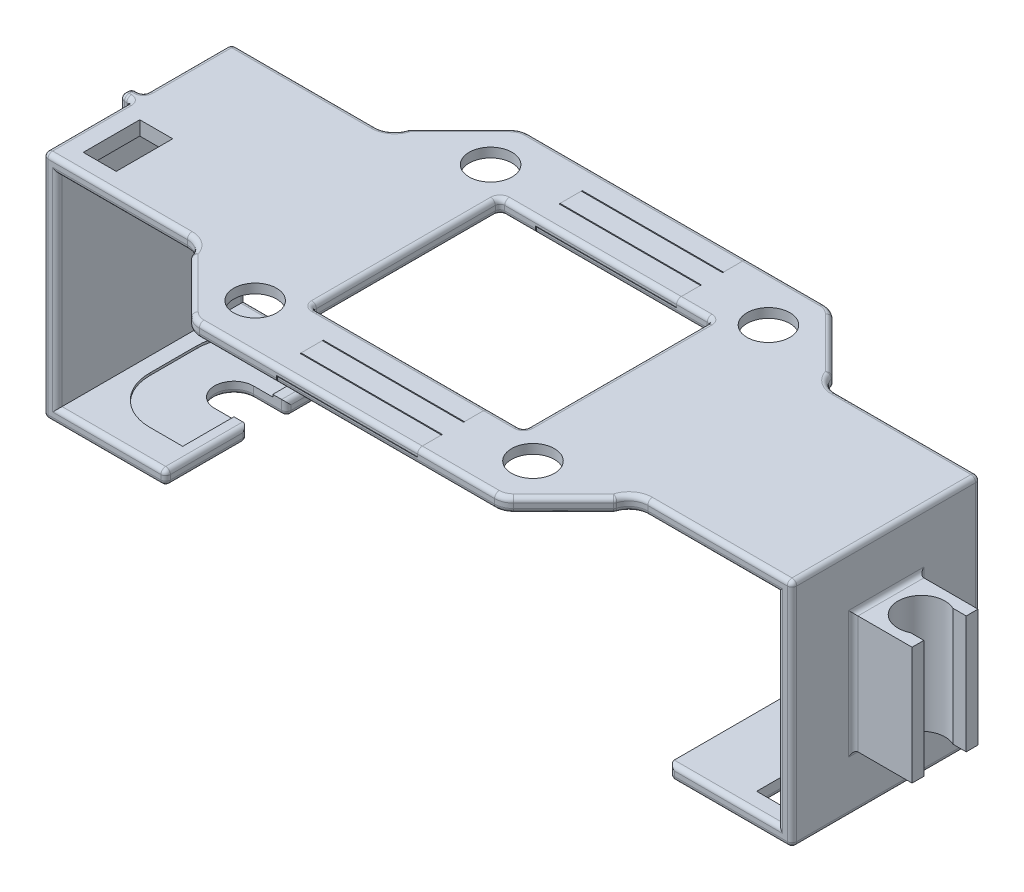
SolidWorks part; units mm, degrees
ref_plane "Front" through (0, 0, 0) normal (0, 0, 1) x (1, 0, 0)
ref_plane "Top" through (0, 0, 0) normal (0, 1, 0) x (1, 0, 0)
ref_plane "Right" through (0, 0, 0) normal (1, 0, 0) x (0, 0, -1)
sketch "Sketch2" plane through (0, 0, 0) normal (0, 1, 0) x (1, 0, 0)
  line L0 (45, -20) -> (52.5, -20)
  line L1 (-52.5, 20) -> (-45, 20)
  line L2 (-52.5, 20) -> (-52.5, -20) construction
  line L3 (-52.5, -20) -> (-45, -20)
  line L4 (52.5, 20) -> (52.5, -20) construction
  line L5 (-52.5, 20) -> (52.5, -20) construction
  line L6 (-52.5, -20) -> (52.5, 20) construction
  line L7 (-52.5, 20) -> (-76.5, 20)
  line L8 (-76.5, 20) -> (-76.5, -20) construction
  line L9 (-76.5, -20) -> (-52.5, -20)
  line L10 (52.5, -20) -> (76.5, -20)
  line L11 (76.5, -20) -> (76.5, 20) construction
  line L12 (76.5, 20) -> (52.5, 20)
  line L13 (-76.5, -20) -> (-79.5, -20)
  line L14 (-79.5, -20) -> (-79.5, 20)
  line L15 (-79.5, 20) -> (-76.5, 20)
  line L16 (76.5, -20) -> (79.5, -20)
  line L17 (79.5, -20) -> (79.5, 20)
  line L18 (79.5, 20) -> (76.5, 20)
  line L19 (-45, 20) -> (-45, 35)
  line L20 (-45, 35) -> (45, 35)
  line L21 (45, 35) -> (45, 20)
  line L22 (45, -20) -> (45, -35)
  line L23 (45, -35) -> (-45, -35)
  line L24 (-45, -35) -> (-45, -20)
  line L25 (45, 20) -> (52.5, 20)
  line L26 (0, -35) -> (0, 35) construction
  dimension "D1" = 40
  dimension "D2" = 105
  dimension "D3" = 24
  dimension "D4" = 3
  dimension "D5" = 15
  dimension "D6" = 90
extrude "Boss-Extrude1" add sketch "Sketch2" along normal blind 3
sketch "Sketch4" plane through (0, 0, -20) normal (0, 0, -1) x (-1, 0, 0)
  line L0 (79.5, 0) -> (79.5, -46)
  line L1 (79.5, -46) -> (53.5, -46)
  line L2 (53.5, -46) -> (53.5, -43)
  line L3 (53.5, -43) -> (76.5, -43)
  line L4 (76.5, -43) -> (76.5, 0)
  line L5 (45, 0) -> (79.5, 0) construction
  line L6 (76.5, 0) -> (79.5, 0)
  line L7 (52.5, 0) -> (76.5, 0) construction
  dimension "D1" = 43
  dimension "D2" = 23
extrude "Boss-Extrude2" add sketch "Sketch4" against normal up to surface (40 mm away) up to face at (62.25, 1.5, 20)
mirror "Mirror1" about plane through (0, 0, 0) normal (1, 0, 0) of "Boss-Extrude2"
sketch "Sketch5" plane through (0, -46, 0) normal (0, -1, 0) x (1, 0, 0)
  line L0 (-53.5, 2.625) -> (-60.5, 2.625)
  line L1 (-53.5, 20) -> (-53.5, -20) construction
  line L2 (-60.5, -5.625) -> (-53.5, -5.625)
  line L3 (-53.5, -5.625) -> (-53.5, 2.625)
  line L4 (-53.5, -20) -> (-79.5, -20) construction
  arc A0 (-60.5, 2.625) -> (-60.5, -5.625) centre (-60.5, -1.5) ccw
  dimension "D1" = 4.125
  dimension "D2" = 7
  dimension "D3" = 18.5
extrude "Cut-Extrude1" cut sketch "Sketch5" against normal up to next
sketch "Sketch7" plane through (0, -46, 0) normal (0, -1, 0) x (1, 0, 0)
  line L2 (53.5, -20) -> (79.5, -20) construction
  line L3 (76.5, 20) -> (76.5, -20) construction
  line L7 (68, 16) -> (75, 16)
  line L8 (68, 16) -> (68, 4)
  line L9 (68, 4) -> (75, 4)
  line L10 (75, 16) -> (75, 4)
  line L11 (68, 16) -> (75, 4) construction
  line L12 (68, 4) -> (75, 16) construction
  point P5 (71.5, 10)
  dimension "D1" = 7
  dimension "D2" = 36
  dimension "D3" = 24
  dimension "D4" = 1.5
extrude "Cut-Extrude3" cut sketch "Sketch7" against normal up to next
sketch "Sketch8" plane through (0, 3, 0) normal (0, 1, 0) x (1, 0, 0)
  line L1 (-75, -4) -> (-68, -4)
  line L2 (-75, -4) -> (-75, -16)
  line L3 (-75, -16) -> (-68, -16)
  line L4 (-68, -4) -> (-68, -16)
  line L5 (-75, -4) -> (-68, -16) construction
  line L6 (-75, -16) -> (-68, -4) construction
  line L7 (68, -16) -> (68, -4) construction
  line L8 (68, -4) -> (75, -4) construction
  line L10 (-76.5, -20) -> (-76.5, 20) construction
  line L11 (-45, 20) -> (-79.5, 20) construction
  point P0 (-71.5, -10)
  dimension "D1" = 1.5
  dimension "D2" = 24
extrude "Cut-Extrude5" cut sketch "Sketch8" against normal up to next
sketch "rib1" plane through (79.5, 0, 0) normal (1, 0, 0) x (0, 0, -1)
  line L0 (0, 3) -> (0, -46) construction
  line L1 (-20, 3) -> (20, 3) construction
  line L2 (-20, -46) -> (20, -46) construction
  line L4 (7, -34) -> (-7, -34)
  line L5 (7, -34) -> (7, -9)
  line L6 (7, -9) -> (-7, -9)
  line L7 (-7, -34) -> (-7, -9)
  line L8 (7, -34) -> (-7, -9) construction
  line L9 (7, -9) -> (-7, -34) construction
  point P6 (0, -21.5)
  point P7 (0, -21.5)
  dimension "D1" = 14
  dimension "D2" = 25
sketch "Rib3" plane through (-79.5, 0, 0) normal (-1, 0, 0) x (0, 0, 1)
  line L0 (0, 3) -> (0, -46) construction
  line L1 (-20, 3) -> (20, 3) construction
  line L2 (20, -46) -> (-20, -46) construction
  line L4 (-1.25, 3) -> (1.25, 3)
  line L5 (-1.25, 3) -> (-1.25, -46)
  line L6 (-1.25, -46) -> (1.25, -46)
  line L7 (1.25, 3) -> (1.25, -46)
  line L8 (-1.25, 3) -> (1.25, -46) construction
  line L9 (-1.25, -46) -> (1.25, 3) construction
  point P6 (0, -21.5)
  dimension "D1" = 2.5
extrude "Boss-Extrude6" add sketch "Rib3" along normal blind 2.5
sketch "Sketch12" plane through (0, -43, 0) normal (0, 1, 0) x (1, 0, 0)
  line L0 (-68.75, 1.5) -> (-60.5, 1.5) construction
  line L2 (-56.375, 16.5) -> (-64.625, 16.5) construction
  line L3 (-56.375, 16.5) -> (-56.375, -13.5) construction
  line L4 (-56.375, -13.5) -> (-64.625, -13.5) construction
  line L5 (-64.625, 16.5) -> (-64.625, -13.5) construction
  line L6 (-56.375, 16.5) -> (-64.625, -13.5) construction
  line L7 (-56.375, -13.5) -> (-64.625, 16.5) construction
  line L8 (-56.375, 16.5) -> (-73.375, 16.5)
  line L9 (-56.375, 16.5) -> (-56.375, -13.5)
  line L10 (-56.375, -13.5) -> (-73.375, -13.5)
  line L11 (-73.375, 16.5) -> (-73.375, -13.5)
  point P3 (-64.625, 1.5)
  dimension "D1" = 8.25
  dimension "D2" = 30
  dimension "D3" = 17
extrude "Cut-Extrude9" cut sketch "Sketch12" against normal blind 0.5
fillet "Fillet10" radius 10 2 edges at (-73.375, -43.25, -16.5) (-73.375, -43.25, 13.5)
extrude "Boss-Extrude7" add sketch "rib1" along normal blind 12.5
sketch "Sketch13" plane through (0, -34, 0) normal (0, -1, 0) x (1, 0, 0)
  line L0 (82, 0) -> (92, 0) construction
  line L1 (92, -4.5) -> (92, 4.5)
  line L2 (92, -7) -> (82, -7) construction
  line L3 (92, 7) -> (79.5, 7) construction
  line L4 (92, -7) -> (82, -7) construction
  line L5 (92, -7) -> (92, 7) construction
  line L6 (92, 7) -> (82, 7) construction
  line L7 (82, -7) -> (82, 7) construction
  line L8 (92, -7) -> (92, -4.5) construction
  line L9 (92, -4.5) -> (89.1794, -4.5)
  line L10 (82, -7) -> (82, -3.75) construction
  line L11 (82, 7) -> (92, 7) construction
  line L12 (82, 7) -> (82, 3.75) construction
  line L13 (89.1794, 4.5) -> (92, 4.5)
  line L14 (92, 7) -> (92, 4.5) construction
  arc A0 (89.1794, 4.5) -> (89.1794, -4.5) centre (87, 0) ccw
  dimension "D2" = 10
  dimension "D1" = 10
  dimension "D3" = 2.5
  dimension "D4" = 2.5
extrude "Cut-Extrude10" cut sketch "Sketch13" against normal through all
chamfer "Chamfer1" distance 12 angle 45 4 edges at (45, 1.5, 35) (-45, 1.5, 35) (-45, 1.5, -35) (45, 1.5, -35)
fillet "Fillet14" radius 4 8 edges at (-33, 1.5, 35) (-45, 1.5, 20) (45, 1.5, 20) (-45, 1.5, -20) (-33, 1.5, -35) (45, 1.5, -20) (33, 1.5, -35) (33, 1.5, 35)
sketch "Sketch24" plane through (0, 0, -35) normal (0, 0, -1) x (-1, 0, 0)
  line L0 (0, -8.7543) -> (0, 8.7543) construction
  line L1 (-31.3431, 3) -> (31.3431, 3) construction
  line L2 (15, -4.5) -> (-15, -4.5) construction
  line L3 (15, -4.5) -> (15, 10.5) construction
  line L4 (15, 10.5) -> (-15, 10.5) construction
  line L5 (-15, -4.5) -> (-15, 10.5) construction
  line L6 (15, -4.5) -> (-15, 10.5) construction
  line L7 (15, 10.5) -> (-15, -4.5) construction
  line L8 (0, 0) -> (0, 3) construction
  line L9 (-31.3431, 0) -> (31.3431, 0) construction
  line L10 (15, 10.5) -> (15, 1.5)
  line L11 (15, 3) -> (0, 3) construction
  line L12 (15, 3) -> (15, 1.5) construction
  line L13 (15, 1.5) -> (0, 1.5) construction
  line L14 (0, 3) -> (0, 1.5) construction
  line L15 (0, 1.5) -> (-15, 1.5) construction
  line L16 (0, 1.5) -> (0, 0) construction
  line L17 (0, 0) -> (-15, 0) construction
  line L18 (-15, 1.5) -> (-15, 0) construction
  line L19 (15, 1.5) -> (-15, 1.5)
  line L20 (-15, 1.5) -> (-15, -4.5)
  point P0 (0, 3)
  point P4 (0, 0)
  dimension "D1" = 30
  dimension "D2" = 15
  dimension "D3" = 1.5
sketch "Sketch23" plane through (0, 0, 0) normal (0, -1, 0) x (-1, 0, 0)
  line L0 (0, -35) -> (0, 35) construction
  line L1 (31.3431, -35) -> (-31.3431, -35) construction
  line L2 (-31.3431, 35) -> (31.3431, 35) construction
  line L3 (0, -35) -> (15, -35) construction
  line L4 (0, -35) -> (0, 35) construction
  line L5 (0, 35) -> (15, 35) construction
  line L6 (15, -35) -> (15, 35) construction
  line L8 (0, -35) -> (-15, -35) construction
  line L9 (0, -35) -> (0, 35)
  line L10 (0, 35) -> (-15, 35) construction
  line L11 (-15, -35) -> (-15, 35) construction
  line L12 (15, -20) -> (-15, -20) construction
  line L13 (15, -20) -> (15, 20) construction
  line L14 (15, 20) -> (-15, 20) construction
  line L15 (-15, -20) -> (-15, 20) construction
  line L16 (15, -20) -> (-15, 20) construction
  line L17 (15, 20) -> (-15, -20) construction
  point P4 (0, 0)
  point P12 (0, 0)
  dimension "D1" = 15
  dimension "D2" = 40
split "Split3" trim tools "Sketch24" bodies to split 121 resulting bodies 133 134
sketch "Sketch33" plane through (0, 0, -35) normal (0, 0, -1) x (-1, 0, 0)
  line L0 (15, -4.5) -> (15, 10.5) construction
  line L1 (15, -4.5) -> (15, 10.5) construction
  line L3 (-15, 1.3) -> (15, 1.3)
  line L4 (-15, 1.3) -> (-15, 1.7)
  line L5 (-15, 1.7) -> (15, 1.7)
  line L6 (15, 1.3) -> (15, 1.7)
  line L7 (-15, 1.3) -> (15, 1.7) construction
  line L8 (-15, 1.7) -> (15, 1.3) construction
  point P2 (0, 1.5)
  dimension "D1" = 0.4
extrude "Cut-Extrude18" cut sketch "Sketch33" against normal through all
sketch "Sketch34" plane through (0, 0, 0) normal (0, -1, 0) x (1, 0, 0)
  line L1 (-29.5, 25) -> (29.5, 25) construction
  line L2 (-29.5, 25) -> (-29.5, -25) construction
  line L3 (-29.5, -25) -> (29.5, -25) construction
  line L4 (29.5, 25) -> (29.5, -25) construction
  line L5 (-29.5, 25) -> (29.5, -25) construction
  line L6 (-29.5, -25) -> (29.5, 25) construction
  line L7 (-22.5, 20) -> (22.5, 20)
  line L8 (-22.5, 20) -> (-22.5, -20)
  line L9 (-22.5, -20) -> (22.5, -20)
  line L10 (22.5, 20) -> (22.5, -20)
  line L11 (-22.5, 20) -> (22.5, -20) construction
  line L12 (-22.5, -20) -> (22.5, 20) construction
  circle A0 centre (-29.5, 25) radius 4.55
  circle A1 centre (29.5, 25) radius 4.55
  circle A2 centre (29.5, -25) radius 4.55
  circle A3 centre (-29.5, -25) radius 4.55
  point P0 (0, 0)
  point P6 (0, 0)
  dimension "D5" = 9.1
  dimension "D1" = 59
  dimension "D2" = 50
  dimension "D3" = 40
  dimension "D4" = 45
extrude "Cut-Extrude19" cut sketch "Sketch34" against normal blind 10
sketch "Sketch38" plane through (0, 0, 0) normal (0, -1, 0) x (1, 0, 0)
  line L0 (-15, 35) -> (-15, -35) construction
  line L1 (15, 35) -> (15, -35) construction
  line L2 (-15, 35) -> (-15, -35) construction
  line L3 (15, 35) -> (15, -35) construction
  line L4 (-15, -20) -> (15, -20) construction
  line L5 (-15, -20) -> (15, -20) construction
  line L6 (0, -20) -> (0, -35) construction
  line L8 (-15, -25.25) -> (15, -25.25) construction
  line L9 (-15, -25.25) -> (-15, -29.75) construction
  line L10 (-15, -29.75) -> (15, -29.75) construction
  line L11 (15, -25.25) -> (15, -29.75) construction
  line L12 (-15, -25.25) -> (15, -29.75) construction
  line L13 (-15, -29.75) -> (15, -25.25) construction
  line L14 (-15, -29.75) -> (15, -29.75)
  line L15 (-15, -29.75) -> (-15, -35)
  line L16 (-15, -35) -> (15, -35)
  line L17 (15, -29.75) -> (15, -35)
  line L18 (-15, -20) -> (15, -20)
  line L19 (-15, -20) -> (-15, -25.25)
  line L20 (-15, -25.25) -> (15, -25.25)
  line L21 (15, -20) -> (15, -25.25)
  point P9 (0, -27.5)
  dimension "D1" = 4.5
extrude "Cut-Extrude23" cut sketch "Sketch38" against normal blind 1.5
sketch "Sketch39" plane through (0, 3, 0) normal (0, 1, 0) x (1, 0, 0)
  line L0 (-15, 35) -> (-15, 29.95)
  line L1 (-15, 20) -> (15, 20) construction
  line L2 (0, -35) -> (0, 35) construction
  line L3 (-15, 35) -> (15, 35) construction
  line L4 (-15, 20) -> (15, 20)
  line L5 (0, -35) -> (0, 35) construction
  line L6 (15, 29.75) -> (-15, 29.75) construction
  line L7 (-15, 25.25) -> (15, 25.25) construction
  line L8 (15, 29.75) -> (-15, 29.75) construction
  line L9 (-15, 25.25) -> (15, 25.25) construction
  line L10 (-15, 35) -> (15, 35)
  line L11 (15, 35) -> (15, 29.95)
  line L12 (-15, 25.05) -> (-15, 20)
  line L13 (15, 25.05) -> (15, 20)
  line L15 (-15, 29.75) -> (15, 29.75) construction
  line L16 (-15, 29.75) -> (-15, 29.95) construction
  line L17 (-15, 29.95) -> (15, 29.95)
  line L18 (15, 29.75) -> (15, 29.95) construction
  line L19 (15, 25.25) -> (-15, 25.25) construction
  line L20 (15, 25.25) -> (15, 25.05) construction
  line L21 (15, 25.05) -> (-15, 25.05)
  line L22 (-15, 25.25) -> (-15, 25.05) construction
  dimension "D1" = 0.2
  dimension "D2" = 0.2
extrude "Boss-Extrude8" add sketch "Sketch39" against normal blind 1.5
mirror "Mirror2" about plane through (0, 0, 0) normal (0, 0, 1) of "Boss-Extrude8", "Cut-Extrude23"
sketch "Sketch41" plane through (0, 0, 0) normal (0, -1, 0) x (1, 0, 0)
  line L0 (-15, -20) -> (15, -20) construction
  line L1 (-15, -20) -> (15, -20) construction
  line L2 (0, -20) -> (0, -35) construction
  line L3 (15, -25.05) -> (-15, -25.05) construction
  line L4 (-15, -29.95) -> (15, -29.95) construction
  line L5 (15, -25.05) -> (-15, -25.05) construction
  line L6 (-15, -29.95) -> (15, -29.95) construction
  line L8 (15, -20) -> (-14.8, -20)
  line L9 (15, -20) -> (15, -25.05)
  line L10 (15, -25.05) -> (-14.8, -25.05)
  line L11 (-14.8, -20) -> (-14.8, -25.05)
  line L12 (15, -35) -> (-14.8, -35)
  line L13 (15, -35) -> (15, -29.95)
  line L14 (15, -29.95) -> (-14.8, -29.95)
  line L15 (-14.8, -35) -> (-14.8, -29.95)
  point P5 (0, -27.5)
  dimension "D1" = 29.8
extrude "Boss-Extrude9" add sketch "Sketch41" against normal blind 1.4 separate body
sketch "Sketch43" plane through (0, 0, 0) normal (0, -1, 0) x (1, 0, 0)
  line L0 (0, 35) -> (-15, 35) construction
  line L1 (-15, 29.95) -> (15, 29.95) construction
  line L2 (0, 35) -> (15, 35) construction
  line L3 (15, 25.05) -> (-15, 25.05) construction
  line L4 (-15, 20) -> (15, 20) construction
  line L5 (0, 35) -> (-15, 35) construction
  line L6 (-15, 29.95) -> (15, 29.95) construction
  line L7 (0, 35) -> (15, 35) construction
  line L8 (15, 25.05) -> (-15, 25.05) construction
  line L9 (-15, 20) -> (15, 20) construction
  line L11 (15, 35) -> (-14.8, 35)
  line L12 (15, 35) -> (15, 29.95)
  line L13 (15, 29.95) -> (-14.8, 29.95)
  line L14 (-14.8, 35) -> (-14.8, 29.95)
  line L15 (15, 25.05) -> (-14.8, 25.05)
  line L16 (15, 25.05) -> (15, 20)
  line L17 (15, 20) -> (-14.8, 20)
  line L18 (-14.8, 25.05) -> (-14.8, 20)
  dimension "D1" = 29.8
extrude "Boss-Extrude10" add sketch "Sketch43" against normal blind 1.4 separate body
combine bodies "Combine7" operation type add bodies to combine 165 164 162 161 145
sketch "Sketch44" plane through (0, 3, 0) normal (0, 1, 0) x (1, 0, 0)
  line L0 (15, -35) -> (15, 35) construction
  line L1 (-15, -20) -> (15, -20) construction
  line L2 (0, -35) -> (-15, -35) construction
  line L3 (0, -35) -> (15, -35) construction
  line L4 (0, -20) -> (0, -35) construction
  line L5 (-15, -20) -> (15, -20)
  line L6 (0, -35) -> (-15, -35)
  line L7 (0, -35) -> (15, -35)
  line L8 (15, -35) -> (15, 35) construction
  line L9 (-15, -20) -> (-15, -25.25)
  line L10 (-15, -25.25) -> (15, -25.25)
  line L11 (-15, -25.25) -> (-15, -29.75) construction
  line L12 (-15, -29.75) -> (15, -29.75)
  line L13 (15, -25.25) -> (15, -29.75) construction
  line L14 (-15, -25.25) -> (15, -29.75) construction
  line L15 (-15, -29.75) -> (15, -25.25) construction
  line L16 (15, -20) -> (15, -25.25)
  line L17 (-15, -29.75) -> (-15, -35)
  line L18 (15, -29.75) -> (15, -35)
  point P4 (0, -27.5)
  dimension "D1" = 4.5
extrude "Cut-Extrude24" cut sketch "Sketch44" against normal blind 1.4
mirror "Mirror4" about plane through (0, 0, 0) normal (0, 0, 1) of "Cut-Extrude24"
sketch "Sketch46" plane through (0, 0, 0) normal (0, -1, 0) x (1, 0, 0)
  circle A0 centre (-29.5, 25) radius 6.5
  circle A1 centre (29.5, 25) radius 6.5
  circle A2 centre (29.5, -25) radius 6.5
  circle A3 centre (-29.5, -25) radius 6.5
  dimension "D1" = 13
extrude "Cut-Extrude25" cut sketch "Sketch46" against normal blind 1
fillet "Fillet18" radius 1 63 edges at (-53.5, -46, 11.3125) (-53.5, -44.5, 20) (-53.5, -43, 11.3125) (-53.5, -44.5, 2.625) (-53.5, -43, -12.8125) (-53.5, -44.5, -20) (-53.5, -46, -12.8125) (-53.5, -44.5, -5.625) (-46.4235, 0, -20.8377) (-46.4235, 3, -20.8377) (-79.5, -21.5, -20) (-66.5, -46, -20) (-65, -43, -20) (-64.1865, 3, -20) (-64.625, -46, -1.5) (-57, -46, -5.625) (-82, -46, 0) (-66.5, -46, 20) (-57, -46, 2.625) (-79.5, -21.5, 20) (-3.75, 3, 20) (-8.1716, 3, 35) (-32.8739, 3, 34.6955) (-39.5858, 3, 28.4142) (-46.4235, 3, 20.8377) (-64.1865, 3, 20) (-39.5858, 3, -28.4142) (-32.8739, 3, -34.6955) (-8.1716, 3, -35) (-3.75, 3, -20) (-22.5, 3, 0) (-82, -21.5, -1.25) (-82, 3, 0) (-82, -21.5, 1.25) (-46.4235, 0, 20.8377) (-65, -43, 20) (-23.1716, 0, -35) (-32.8739, 0, -34.6955) (-45, 1.5, -23) (-39.5858, 0, -28.4142) (-23.1716, 0, 35) (-32.8739, 0, 34.6955) (-45, 1.5, 23) (-39.5858, 0, 28.4142) (-18.75, 0, -20) (-18.75, 0, 20) (-22.5, 1.5, -20) (-22.5, 0, 0) (-22.5, 1.5, 20)
fillet "Fillet19" radius 1 51 edges at (8.2716, 0, 35) (32.8739, 0, 34.6955) (23.1716, 3, 35) (32.8739, 3, 34.6955) (46.4235, 0, 20.8377) (46.4235, 3, 20.8377) (46.4235, 3, -20.8377) (46.4235, 0, -20.8377) (23.1716, 3, -35) (32.8739, 3, -34.6955) (8.2716, 0, -35) (32.8739, 0, -34.6955) (45, 1.5, 23) (39.5858, 0, 28.4142) (39.5858, 3, 28.4142) (53.5, -44.5, 20) (65, -43, 20) (76.5, -21.5, 20) (62.6865, 0, 20) (64.1865, 3, 20) (79.5, -34, 0) (79.5, -21.5, -7) (79.5, -9, 0) (79.5, -21.5, 7) (79.5, 3, 0) (79.5, -21.5, 20) (53.5, -46, 0) (66.5, -46, 20) (79.5, -46, 0) (71.5, -46, 4) (75, -46, 10) (71.5, -46, 16) (68, -46, 10) (76.5, -21.5, -20) (65, -43, -20) (53.5, -44.5, -20) (66.5, -46, -20) (79.5, -21.5, -20) (64.1865, 3, -20) (62.6865, 0, -20) (45, 1.5, -23) (39.5858, 3, -28.4142) (39.5858, 0, -28.4142) (18.75, 3, -20) (18.75, 3, 20) (22.5, 3, 0) (22.5, 1.5, 20) (22.5, 0, 0) (22.5, 1.5, -20) (3.85, 0, -20) (3.85, 0, 20)
